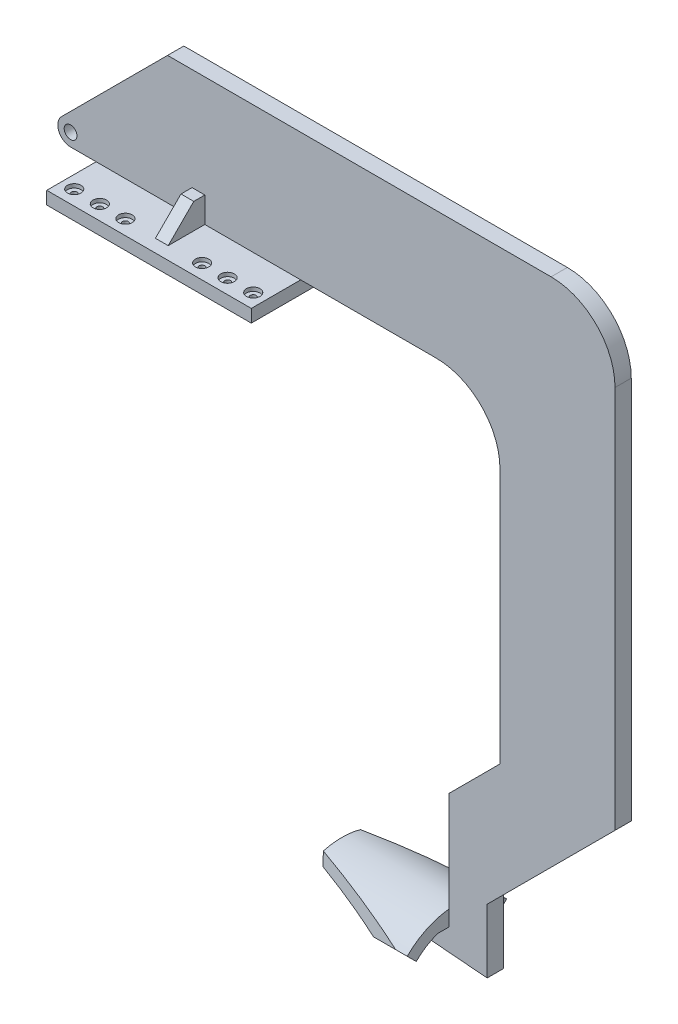
SolidWorks part; units mm, degrees
material "Stainless Steel (ferritic)"
ref_plane "Front Plane" through (0, 0, 0) normal (0, 0, 1) x (1, 0, 0)
ref_plane "Top Plane" through (0, 0, 0) normal (0, 1, 0) x (1, 0, 0)
ref_plane "Right Plane" through (0, 0, 0) normal (1, 0, 0) x (0, 0, -1)
sketch "Sketch1" plane through (0, 0, 0) normal (0, 0, 1) x (1, 0, 0)
  line L0 (-7.0711, 7.0711) -> (75.8579, 90)
  line L1 (75.8579, 90) -> (375.8579, 90)
  line L2 (425.8579, 40) -> (425.8579, -260)
  line L3 (425.8579, -260) -> (325.8579, -360)
  line L4 (325.8579, -360) -> (325.8579, -410)
  line L5 (325.8579, -410) -> (205.8579, -400)
  line L6 (205.8579, -400) -> (205.8579, -380)
  line L7 (205.8579, -380) -> (295.8579, -380)
  line L8 (295.8579, -380) -> (295.8579, -40) construction
  line L9 (285.8579, -10) -> (0, -10)
  line L10 (295.8579, -300) -> (335.8579, -260)
  line L11 (335.8579, -260) -> (335.8579, -60)
  line L12 (295.8579, -300) -> (295.8579, -380)
  arc A0 (295.8579, -40) -> (285.8579, -10) centre (245.8579, -40) ccw construction
  arc A1 (375.8579, 90) -> (425.8579, 40) centre (375.8579, 40) cw
  arc A2 (-7.0711, 7.0711) -> (0, -10) centre (0, 0) ccw
  circle A3 centre (0, 0) radius 5
  arc A4 (285.8579, -10) -> (335.8579, -60) centre (285.8579, -60) cw
  point P24 (295.8579, -10)
  point P27 (425.8579, 90)
  dimension "D11" = 50
  dimension "D12" = 20
  dimension "D13" = 10
  dimension "D15" = 50
  dimension "D1" = 500
  dimension "D2" = 100
  dimension "D3" = 130
  dimension "D4" = 30
  dimension "D5" = 45
  dimension "D6" = 350
  dimension "D7" = 370
  dimension "D8" = 10
  dimension "D9" = 350
  dimension "D10" = 120
  dimension "D14" = 90
extrude "Boss-Extrude1" add sketch "Sketch1" along normal blind 30
sketch "Sketch2" plane through (0, -10, 0) normal (0, -1, 0) x (1, 0, 0)
  line L0 (0, 30) -> (0, 0) construction
  line L1 (20, -30) -> (180, -30)
  line L2 (20, -30) -> (20, 60)
  line L3 (20, 60) -> (180, 60)
  line L4 (180, -30) -> (180, 60)
  line L5 (0, 30) -> (0, 0)
  point P6 (0, 15)
  point P7 (20, 15)
  line M3 (0, 0) -> (285.8579, 0)
  line M5 (285.8579, 30) -> (0, 30)
  dimension "D1" = 160
  dimension "D2" = 90
  dimension "D3" = 20
extrude "Boss-Extrude2" add sketch "Sketch2" along normal blind 10 contours L4 L3 L2 M5 | L4 L2 M3 M5 | L1 L4 L2 M3 region at (100, -10, -15) region at (100, -10, 15) region at (100, -10, 45)
ref_plane "Plane2" through (100, 0, 0) normal (-1, 0, 0) x (0, 0, 1)
sketch "Sketch5" plane through (100, 0, 0) normal (-1, 0, 0) x (0, 0, 1)
  line L0 (30, 10) -> (50, -10)
  line L1 (30, -10) -> (30, 7.0711) construction
  line L2 (30, -10) -> (60, -10) construction
  line L3 (30, 90) -> (30, 7.0711) construction
  dimension "D1" = 10
  dimension "D2" = 20
rib "Rib1" sketch "Sketch5" sketch "Sketch5" thickness 10 extrusion direction parallel to sketch draft on no parameters "D1"=10
sketch "Sketch7" plane through (100, 0, 0) normal (-1, 0, 0) x (0, 0, 1)
  line L0 (0, 10) -> (-20, -10)
  line L1 (0, 90) -> (0, 7.0711) construction
  line L2 (-30, -10) -> (0, -10) construction
  dimension "D1" = 20
  dimension "D2" = 10
rib "Rib17" sketch "Sketch7" sketch "Sketch7" thickness 10 extrusion direction parallel to sketch draft on no parameters "D1"=10
sketch "Sketch8" plane through (0, -20, 0) normal (0, -1, 0) x (1, 0, 0)
  line L0 (20, 0) -> (95, 0) construction
  line L1 (105, 0) -> (180, 0) construction
  line L2 (105, 30) -> (180, 30) construction
  line L3 (20, 30) -> (95, 30) construction
  line L4 (20, 0) -> (95, 0)
  line L5 (105, 0) -> (180, 0)
  line L6 (105, 30) -> (180, 30)
  line L7 (20, 30) -> (95, 30)
  line L8 (180, 0) -> (180, 30) construction
  line L9 (180, 0) -> (180, 30)
  line L10 (40, 45) -> (40, -15) construction
  line L11 (20, 60) -> (20, 30) construction
  line L12 (40, 45) -> (75, 45) construction
  line L13 (125, 45) -> (160, 45) construction
  circle A0 centre (40, 45) radius 7.5
  circle A1 centre (75, 45) radius 7.5
  circle A2 centre (125, 45) radius 7.5
  circle A3 centre (160, 45) radius 7.5
  circle A4 centre (40, -15) radius 7.5
  circle A5 centre (75, -15) radius 7.5
  circle A6 centre (125, -15) radius 7.5
  circle A7 centre (160, -15) radius 7.5
  point P24 (180, 15)
  point P25 (40, 15)
  point P26 (57.5, 45)
  point P27 (20, 45)
  point P28 (57.5, 30)
  point P29 (142.5, 45)
  point P30 (142.5, 30)
  dimension "D1" = 15
  dimension "D2" = 35
  dimension "D3" = 35
extrude "Cut-Extrude1" [suppressed] cut sketch "Sketch8" against normal blind 10 contours A0 | A1 | A4 | A5 | A6 | A7 | A3 | A2
sketch "Sketch10" [suppressed] plane through (-31.6148, -379.3773, 0) normal (-0.083, -0.9965, 0) x (0.9965, -0.083, 0)
  line L4 (357.4542, 53.8909) -> (248.3304, 30)
  line L5 (357.4542, -23.8909) -> (248.3304, 0)
  line L9 (351.9262, 52.6806) -> (233.6057, 26.7763)
  line L10 (233.6057, 26.7763) -> (233.6057, 62.0562)
  line L11 (233.6057, 62.0562) -> (351.9262, 52.6806)
  line L15 (248.3304, 30) -> (368.7464, 30) construction
  line L16 (354.1513, -23.1678) -> (238.1443, 2.2301)
  line L17 (238.1443, 2.2301) -> (238.1443, -32.7213)
  line L18 (238.1443, -32.7213) -> (354.1513, -23.1678)
  line L19 (248.3304, 0) -> (368.7464, 0) construction
  ellipse E0 centre (360.6839, 15) end of major axis (360.6839, 70) minor radius 4.5675 (356.2896, 0) -> (357.4542, -23.8909) ccw construction
  ellipse E1 centre (360.6839, 15) end of major axis (360.6839, 70) minor radius 4.5675 (357.4542, 53.8909) -> (356.2896, 30) ccw construction
  ellipse E2 centre (360.6839, 15) end of major axis (360.6839, 70) minor radius 4.5675 (356.2896, 0) -> (357.4542, -23.8909) ccw
  ellipse E3 centre (360.6839, 15) end of major axis (360.6839, 70) minor radius 4.5675 (357.4542, 53.8909) -> (356.2896, 30) ccw
  dimension "D1" = 32.7213
  dimension "D2" = 116.007
  dimension "D3" = 35.2799
  dimension "D4" = 118.3205
  dimension "D5" = 32.0562
  dimension "D6" = 10.1861
extrude "Cut-Extrude3" [suppressed] cut sketch "Sketch10" against normal blind 30 contours L9 L10 L11 | L18 L16 L17
sketch "Sketch11" plane through (0, -10, 0) normal (0, 1, 0) x (1, 0, 0)
  point P0 (170, 16.5)
  point P1 (150, 16.5)
  point P3 (150, -48.5)
  point P5 (170, -48.5)
sketch "Sketch14" plane through (0, -10, 0) normal (0, 1, 0) x (1, 0, 0)
  point P0 (130, -48.5)
  dimension "D1" = 20
ref_plane "Plane3" through (100, 0, 0) normal (1, 0, 0) x (0, 0, -1)
hole_wizard "CBORE for M4 Hex Head Machine Screw2" positions "Sketch15" profile "Sketch16" counterbore size "M4" standard "ANSI Metric" end condition through all
sketch "Sketch15" plane through (0, -10, 0) normal (0, 1, 0) x (1, 0, 0)
  point P0 (130, -48.5)
  point P3 (150, -48.5)
  point P6 (170, -48.5)
sketch "Sketch16" plane through (130, -10, 48.5) normal (1, 0, 0) x (0, 0, 1)
  line L0 (0, 0) -> (0, 400)
  line L1 (0, 400) -> (2.25, 400)
  line L3 (2.25, 400) -> (2.25, 3)
  line L4 (2.25, 3) -> (5.295, 3)
  line L5 (5.295, 3) -> (5.295, 0)
  line L7 (5.295, 0) -> (0, 0)
  line L11 (0, -6.35) -> (0, 107.95) construction
  dimension "Thru Hole Dia." = 4.5
  dimension "Thru Hole Depth" = 400
  dimension "C'Bore Dia." = 10.59
  dimension "C'Bore Depth" = 3
mirror "Mirror1" about plane through (100, 0, 0) normal (1, 0, 0) of "CBORE for M4 Hex Head Machine Screw2"
ref_plane "Plane4" through (0, 0, 16) normal (0, 0, 1) x (1, 0, 0)
mirror "Mirror2" about plane through (0, 0, 16) normal (0, 0, 1) of "Mirror1", "CBORE for M4 Hex Head Machine Screw2"
sketch "Sketch19" plane through (295.8579, 0, 0) normal (-1, 0, 0) x (0, 0, 1)
  line L0 (-23.8909, -394.0242) -> (-16.8198, -401.0952)
  line L1 (46.8198, -401.0952) -> (53.8909, -394.0242)
  line L2 (15, -432.915) -> (15, -326.0199) construction
  line L3 (53.8909, -394.0242) -> (15, -432.915) construction
  line L4 (15, -432.915) -> (-23.8909, -394.0242) construction
  arc A0 (53.8909, -394.0242) -> (-23.8909, -394.0242) centre (15, -432.915) ccw
  arc A1 (46.8198, -401.0952) -> (-16.8198, -401.0952) centre (15, -432.915) ccw
  circle A2 centre (15, -432.915) radius 55 construction
  circle A3 centre (15, -432.915) radius 45 construction
  dimension "D1" = 110
  dimension "D3" = 90
  dimension "D2" = 10
extrude "Boss-Extrude5" add sketch "Sketch19" along normal up to surface (90 mm away) up to face at (205.8579, -390, 15)
sketch "Sketch20" plane through (-31.6837, -380.2049, 0) normal (-0.083, -0.9965, 0) x (0.9965, -0.083, 0)
  line L4 (346.4993, 62.2427) -> (238.365, 30)
  line L5 (344.1859, -32.1821) -> (238.365, 0)
  line L9 (346.4993, 62.2427) -> (228.1788, 26.9628)
  line L10 (228.1788, 26.9628) -> (228.1788, 62.2427)
  line L11 (228.1788, 62.2427) -> (346.4993, 62.2427)
  line L16 (344.1859, -32.1821) -> (228.1788, 3.0978)
  line L17 (228.1788, 3.0978) -> (228.1788, -32.1821)
  line L18 (228.1788, -32.1821) -> (344.1859, -32.1821)
  dimension "D2" = 116.007
  dimension "D3" = 35.2799
  dimension "D4" = 118.3205
  dimension "D6" = 10.1861
extrude "Cut-Extrude4" cut sketch "Sketch20" against normal blind 100 and the other way blind 100 contours L17 L18 L5 L16 | L11 L10 L9 L4 region at (235.0108, -402.4294, 50.4827) region at (234.2423, -402.3654, -20.4222)
sketch "Sketch21" plane through (0, 0, 30) normal (0, 0, 1) x (1, 0, 0)
  line L0 (206.6505, -390.4886) -> (205.8579, -390.4886)
  line L1 (205.8579, -400) -> (205.8579, -379.8612) construction
  line L2 (205.8579, -390.4886) -> (205.8579, -400)
  line L19 (295.8579, -390.4886) -> (206.6505, -390.4886)
  line L20 (206.6505, -390.4886) -> (205.8579, -400)
  line L21 (205.8579, -400) -> (325.8579, -410)
  line L22 (325.8579, -410) -> (325.8579, -360)
  line L23 (325.8579, -360) -> (425.8579, -260)
  line L24 (425.8579, -260) -> (425.8579, 40)
  line L25 (375.8579, 90) -> (75.8579, 90)
  line L26 (75.8579, 90) -> (-7.0711, 7.0711)
  line L27 (0, -10) -> (20, -10)
  line L28 (20, -10) -> (95, -10)
  line L29 (95, -10) -> (95, 10)
  line L30 (95, 10) -> (105, 10)
  line L31 (105, 10) -> (105, -10)
  line L32 (105, -10) -> (180, -10)
  line L33 (180, -10) -> (285.8579, -10)
  line L34 (335.8579, -60) -> (335.8579, -260)
  line L35 (335.8579, -260) -> (295.8579, -300)
  line L36 (295.8579, -300) -> (295.8579, -380)
  line L37 (295.8579, -380) -> (295.8579, -390.4886)
  line L38 (295.8579, -390.4886) -> (206.6505, -390.4886)
  line L39 (206.6505, -390.4886) -> (205.8579, -400) construction
  line L40 (205.8579, -400) -> (325.8579, -410)
  line L41 (325.8579, -410) -> (325.8579, -360)
  line L42 (325.8579, -360) -> (425.8579, -260)
  line L43 (425.8579, -260) -> (425.8579, 40)
  line L44 (375.8579, 90) -> (75.8579, 90)
  line L45 (75.8579, 90) -> (-7.0711, 7.0711)
  line L46 (0, -10) -> (20, -10)
  line L47 (20, -10) -> (95, -10)
  line L48 (95, -10) -> (95, 10)
  line L49 (95, 10) -> (105, 10)
  line L50 (105, 10) -> (105, -10)
  line L51 (105, -10) -> (180, -10)
  line L52 (180, -10) -> (285.8579, -10)
  line L53 (335.8579, -60) -> (335.8579, -260)
  line L54 (335.8579, -260) -> (295.8579, -300)
  line L55 (295.8579, -300) -> (295.8579, -380)
  line L56 (295.8579, -380) -> (295.8579, -390.4886)
  arc A3 (425.8579, 40) -> (375.8579, 90) centre (375.8579, 40) ccw
  arc A4 (-7.0711, 7.0711) -> (0, -10) centre (0, 0) ccw
  arc A5 (335.8579, -60) -> (285.8579, -10) centre (285.8579, -60) ccw
  arc A6 (425.8579, 40) -> (375.8579, 90) centre (375.8579, 40) ccw
  arc A7 (-7.0711, 7.0711) -> (0, -10) centre (0, 0) ccw
  arc A8 (335.8579, -60) -> (285.8579, -10) centre (285.8579, -60) ccw
  dimension "D1" = 0
extrude "Cut-Extrude5" cut sketch "Sketch21" against normal blind 8.65
sketch "Sketch22" plane through (0, 0, 0) normal (0, 0, -1) x (-1, 0, 0)
  line L0 (-206.6505, -390.4886) -> (-205.8579, -390.4886)
  line L1 (-205.8579, -390.4886) -> (-205.8579, -400)
  line L19 (-325.8579, -410) -> (-205.8579, -400)
  line L20 (-205.8579, -400) -> (-206.6505, -390.4886)
  line L21 (-206.6505, -390.4886) -> (-295.8579, -390.4886)
  line L22 (-295.8579, -390.4886) -> (-295.8579, -380)
  line L23 (-295.8579, -380) -> (-295.8579, -300)
  line L24 (-295.8579, -300) -> (-335.8579, -260)
  line L25 (-335.8579, -260) -> (-335.8579, -60)
  line L26 (-285.8579, -10) -> (-180, -10)
  line L27 (-180, -10) -> (-105, -10)
  line L28 (-105, -10) -> (-105, 10)
  line L29 (-105, 10) -> (-95, 10)
  line L30 (-95, 10) -> (-95, -10)
  line L31 (-95, -10) -> (-20, -10)
  line L32 (-20, -10) -> (0, -10)
  line L33 (7.0711, 7.0711) -> (-75.8579, 90)
  line L34 (-75.8579, 90) -> (-375.8579, 90)
  line L35 (-425.8579, 40) -> (-425.8579, -260)
  line L36 (-425.8579, -260) -> (-325.8579, -360)
  line L37 (-325.8579, -360) -> (-325.8579, -410)
  line L38 (-325.8579, -410) -> (-205.8579, -400)
  line L39 (-205.8579, -400) -> (-206.6505, -390.4886) construction
  line L40 (-206.6505, -390.4886) -> (-295.8579, -390.4886)
  line L41 (-295.8579, -390.4886) -> (-295.8579, -380)
  line L42 (-295.8579, -380) -> (-295.8579, -300)
  line L43 (-295.8579, -300) -> (-335.8579, -260)
  line L44 (-335.8579, -260) -> (-335.8579, -60)
  line L45 (-285.8579, -10) -> (-180, -10)
  line L46 (-180, -10) -> (-105, -10)
  line L47 (-105, -10) -> (-105, 10)
  line L48 (-105, 10) -> (-95, 10)
  line L49 (-95, 10) -> (-95, -10)
  line L50 (-95, -10) -> (-20, -10)
  line L51 (-20, -10) -> (0, -10)
  line L52 (7.0711, 7.0711) -> (-75.8579, 90)
  line L53 (-75.8579, 90) -> (-375.8579, 90)
  line L54 (-425.8579, 40) -> (-425.8579, -260)
  line L55 (-425.8579, -260) -> (-325.8579, -360)
  line L56 (-325.8579, -360) -> (-325.8579, -410)
  arc A3 (-285.8579, -10) -> (-335.8579, -60) centre (-285.8579, -60) ccw
  arc A4 (0, -10) -> (7.0711, 7.0711) centre (0, 0) ccw
  arc A5 (-375.8579, 90) -> (-425.8579, 40) centre (-375.8579, 40) ccw
  arc A6 (-285.8579, -10) -> (-335.8579, -60) centre (-285.8579, -60) ccw
  arc A7 (0, -10) -> (7.0711, 7.0711) centre (0, 0) ccw
  arc A8 (-375.8579, 90) -> (-425.8579, 40) centre (-375.8579, 40) ccw
  dimension "D1" = 0
extrude "Cut-Extrude6" cut sketch "Sketch22" against normal blind 8.65
